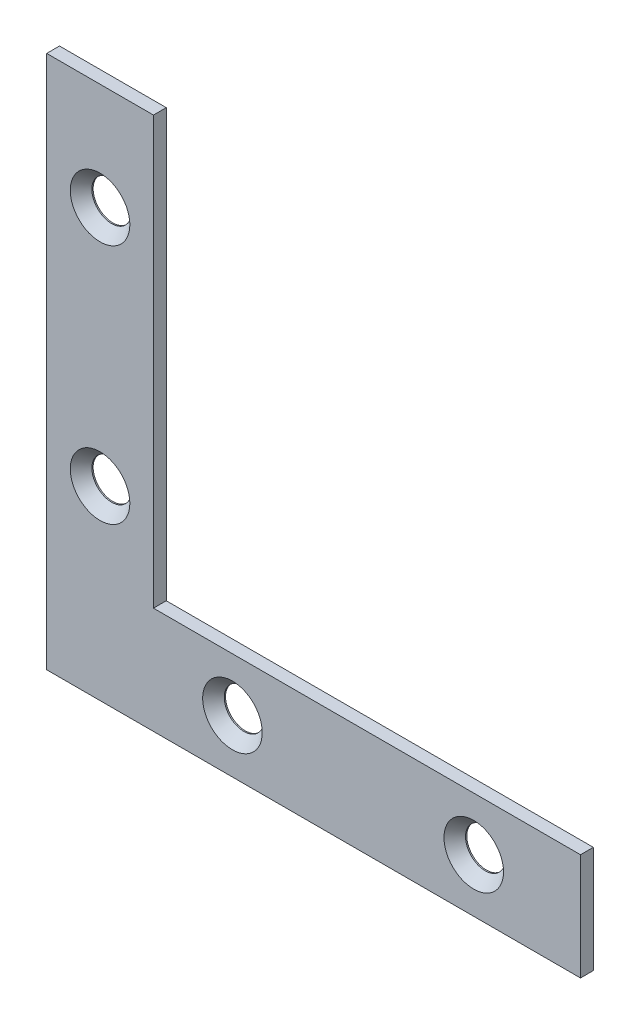
SolidWorks part; units mm, degrees
ref_plane "Front Plane" through (0, 0, 0) normal (0, 0, 1) x (1, 0, 0)
ref_plane "Top Plane" through (0, 0, 0) normal (0, 1, 0) x (1, 0, 0)
ref_plane "Right Plane" through (0, 0, 0) normal (1, 0, 0) x (0, 0, -1)
sketch "Sketch1" plane through (0, 0, 0) normal (0, 0, 1) x (1, 0, 0)
  line L0 (-31.75, 31.75) -> (-31.75, -31.75) construction
  line L1 (-31.75, -31.75) -> (31.75, -31.75) construction
  line L2 (31.75, -31.75) -> (31.75, -19.05) construction
  line L3 (31.75, -19.05) -> (-19.05, -19.05) construction
  line L4 (-19.05, -19.05) -> (-19.05, 31.75) construction
  line L5 (-19.05, 31.75) -> (-31.75, 31.75) construction
  line L6 (-31.75, -31.75) -> (31.75, 31.75) construction
  line L7 (-25.4, 31.75) -> (-25.4, -25.4) construction
  line L8 (-25.4, -25.4) -> (31.75, -25.4) construction
  line L9 (-12.1575, -27.9055) -> (-7.1465, -22.8945) construction
  circle A0 centre (-9.652, -25.4) radius 2.3495 construction
  point P10 (-25.4, -9.652)
  point P11 (-25.4, 19.05)
  point P12 (-9.652, -25.4)
  point P13 (19.05, -25.4)
  dimension "Hole Size" = 4.699
  dimension "Length (A)" = 63.5
  dimension "Length (C)" = 63.5
  dimension "Length (B)" = 12.7
  dimension "Hole Spacing (A)" = 28.702
  dimension "Hole Offset (A)" = 12.7
  dimension "Hole Offset (C)" = 12.7
  dimension "Hole Spacing (C)" = 28.702
  dimension "D1" = 45
  dimension "C'Sink Size" = 7.0866
sketch "Sketch2" plane through (0, 0, 0) normal (1, 0, 0) x (0, 0, -1)
  line L0 (0.762, 31.75) -> (-0.762, 31.75)
  dimension "Thickness" = 1.524
sketch "Sketch3" plane through (0, 0, 0) normal (0, 0, 1) x (1, 0, 0)
  line L0 (-31.75, 31.75) -> (-19.05, 31.75)
  line L1 (-19.05, 31.75) -> (-19.05, -19.05)
  line L2 (-19.05, -19.05) -> (31.75, -19.05)
  line L3 (31.75, -19.05) -> (31.75, -31.75)
  line L4 (31.75, -31.75) -> (-31.75, -31.75)
  line L5 (-31.75, -31.75) -> (-31.75, 31.75)
extrude "Boss-Extrude1" add sketch "Sketch3" along normal up to vertex (0.762 mm away) and the other way up to vertex (0.762 mm away) up to point (0, 31.75, 0.762) other way up to point (0, 31.75, -0.762)
sketch "Sketch4" plane through (0, 0, 0) normal (0, 0, 1) x (1, 0, 0)
  line L0 (-12.1575, -27.9055) -> (-7.1465, -22.8945) construction
  circle A0 centre (-25.4, 19.05) radius 2.3495
  circle A1 centre (-25.4, -9.652) radius 2.3495
  circle A2 centre (-9.652, -25.4) radius 2.3495
  circle A3 centre (19.05, -25.4) radius 2.3495
  circle A4 centre (-9.652, -25.4) radius 2.3495 construction
extrude "Cut-Extrude1" cut sketch "Sketch4" against normal through all both and the other way through all
sketch "Sketch5" plane through (0, 0, 0.762) normal (0, 0, 1) x (1, 0, 0)
  line L0 (-25.4, 31.75) -> (-25.4, -25.4) construction
  line L1 (-12.1575, -27.9055) -> (-7.1465, -22.8945) construction
  circle A0 centre (-25.4, 19.05) radius 3.5433
  circle A1 centre (-25.4, -9.652) radius 3.5433
  circle A2 centre (-9.652, -25.4) radius 3.5433
  circle A3 centre (19.05, -25.4) radius 3.5433
extrude "Cut-Extrude2" cut sketch "Sketch5" against normal through all draft 41
equation "\"Hole Spacing (A)@Sketch1\"=\"Hole Spacing (C)@Sketch1\""
equation "\"Hole Offset (A)@Sketch1\"=\"Hole Offset (C)@Sketch1\""
